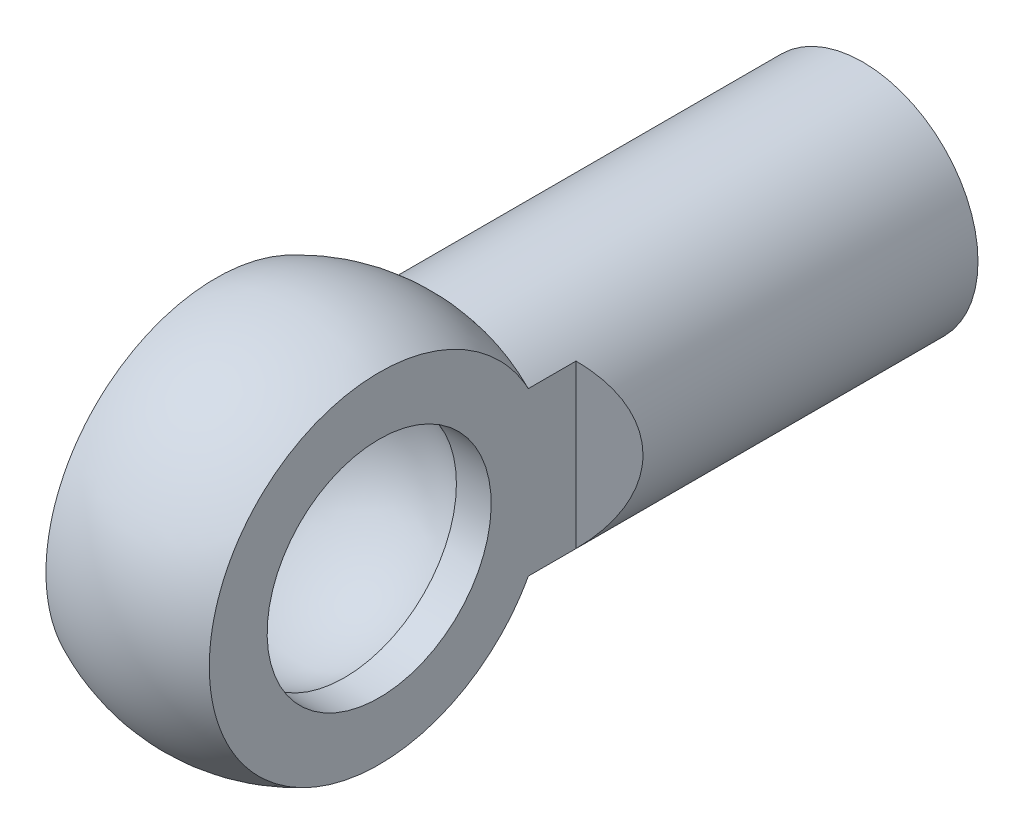
SolidWorks part; units mm, degrees
material "ABS"
ref_plane "Спереди" through (0, 0, 0) normal (0, 0, 1) x (1, 0, 0)
ref_plane "Сверху" through (0, 0, 0) normal (0, 1, 0) x (1, 0, 0)
ref_plane "Справа" through (0, 0, 0) normal (1, 0, 0) x (0, 0, -1)
sketch "Эскиз1" plane through (0, 0, 0) normal (0, 1, 0) x (1, 0, 0)
  line L0 (0, 0) -> (0, -4.5)
  line L2 (0, 0) -> (0, 13.5)
  line L3 (0, 13.5) -> (2.75, 13.5)
  line L4 (2.75, 3.562) -> (2.75, 13.5)
  line L5 (0, 4.5) -> (1.5, 4.5)
  line L6 (0, 4.5) -> (0, 13.5)
  line L7 (0, 13.5) -> (1.5, 13.5)
  line L8 (1.5, 4.5) -> (1.5, 13.5)
  arc A0 (0, -4.5) -> (2.75, 3.562) centre (0, 0) ccw
  arc A1 (0, -2.9) -> (0, 2.9) centre (0, 0) ccw
  dimension "D1" = 4.5
  dimension "D4" = 2.9
  dimension "D2" = 2.75
  dimension "D3" = 18
  dimension "D5" = 9
  dimension "D6" = 1.5
revolve "Повернуть1" add sketch "Эскиз1" angle 360 about L2 region at (2.2858, 0, -3.4144)
sketch "Эскиз2" plane through (0, 0, 0) normal (0, 0, 1) x (1, 0, 0)
  line L1 (-1.95, 5) -> (1.95, 5)
  line L2 (-1.95, 5) -> (-1.95, -5)
  line L3 (-1.95, -5) -> (1.95, -5)
  line L4 (1.95, 5) -> (1.95, -5)
  line L5 (-1.95, 5) -> (1.95, -5) construction
  line L6 (-1.95, -5) -> (1.95, 5) construction
  point P0 (0, 0)
  dimension "D1" = 3.9
  dimension "D2" = 10
extrude "Вырез-Вытянуть2" cut sketch "Эскиз2" against normal blind 5.5 and the other way blind 5.5 flip side to cut contours L2 L3 L4 L1
chamfer "Фаска2" distance 0.8 angle 45 2 edges at (1.95, 0, -5.5) (-1.95, 0, -5.5) tangent propagation no
sketch "Эскиз3" plane through (1.95, 0, 0) normal (1, 0, 0) x (0, 0, -1)
  circle A0 centre (0, 0) radius 2.675
  dimension "D1" = 5.35
extrude "Вырез-Вытянуть3" cut sketch "Эскиз3" against normal up to next
